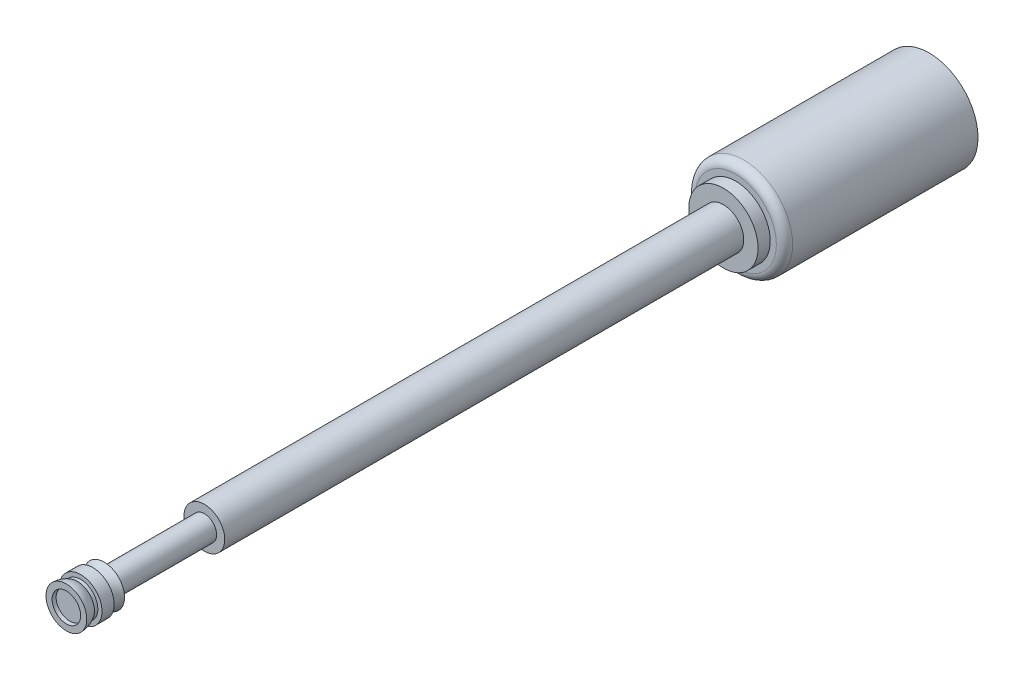
SolidWorks part; units mm, degrees
ref_plane "Front Plane" through (0, 0, 0) normal (0, 0, 1) x (1, 0, 0)
ref_plane "Top Plane" through (0, 0, 0) normal (0, 1, 0) x (1, 0, 0)
ref_plane "Right Plane" through (0, 0, 0) normal (1, 0, 0) x (0, 0, -1)
sketch "Sketch2" plane through (0, 0, 0) normal (0, 0, 1) x (1, 0, 0)
  circle A0 centre (0, 0) radius 0.5
  circle A1 centre (0, 0) radius 1.2
  dimension "D1" = 1
  dimension "D2" = 2.4
extrude "Boss-Extrude1" add sketch "Sketch2" along normal blind 15.5 contours A0 region at (0, 0, 0)
extrude "Boss-Extrude2" add sketch "Sketch2<3>" against normal blind 4.75 contours A1
sketch "Sketch2<3>" plane through (0, 0, 0) normal (0, 0, 1) x (1, 0, 0) same geometry as "Sketch2"
fillet "Fillet1" radius 0.2 1 edges at (1.2, 0, 0)
sketch "Sketch3" plane through (0, 0, 0) normal (0, 0, 1) x (1, 0, 0)
  circle A0 centre (0, 0) radius 0.85
  dimension "D1" = 1.7
extrude "Boss-Extrude3" add sketch "Sketch3" along normal blind 0.3
sketch "Sketch4" plane through (0, 0, 0) normal (0, 1, 0) x (1, 0, 0)
  line L0 (0.5, -15.5) -> (0, -15.5)
  line L1 (-0.5, -15.5) -> (0.5, -15.5) construction
  line L2 (0, -15.5) -> (0, -16.0775)
  line L3 (0.35, -16.4275) -> (0.5, -16.4275)
  line L4 (0.4214, -16.1584) -> (0.4214, -16.0764)
  line L5 (0.4214, -16.0764) -> (0.5238, -16.0764)
  line L6 (0.5238, -16.0764) -> (0.5238, -15.7784)
  line L7 (0.5238, -15.7784) -> (0.4214, -15.7784)
  arc A0 (0, -16.0775) -> (0.35, -16.4275) centre (0, -16.4275) cw
  arc A1 (0.5, -16.4275) -> (0.4214, -16.1584) centre (0, -16.4275) ccw
  arc A2 (0.4214, -15.7784) -> (0.5, -15.5) centre (0.9538, -15.7784) cw
  point P20 (0.425, -16.4275)
  dimension "D2" = 0.35
  dimension "D3" = 0.5
  dimension "D1" = 0.9275
revolve "Revolve1" add sketch "Sketch4" angle 360 about L2
sketch "Sketch5" plane through (0, 0, 0) normal (0, 1, 0) x (1, 0, 0)
  line L0 (0, -15.5) -> (0, -16.4275) construction
  line L1 (0.5, -15.5) -> (-0.5, -15.5) construction
  line L2 (-0.5, -16.4275) -> (0.5, -16.4275) construction
  line L4 (0, -16.3107) -> (-0.4525, -16.3107)
  line L5 (0, -16.3107) -> (0, -16.34)
  line L6 (0, -16.34) -> (-0.4525, -16.34)
  line L7 (-0.4525, -16.3107) -> (-0.4525, -16.34)
  line L8 (0, -16.3107) -> (-0.4525, -16.34) construction
  line L9 (0, -16.34) -> (-0.4525, -16.3107) construction
  point P10 (-0.2262, -16.3254)
  dimension "D1" = 0.84
revolve "Revolve2" add sketch "Sketch5" angle 360 about L0
sketch "Sketch6" plane through (0, 0, 0) normal (0, 1, 0) x (1, 0, 0)
  line L0 (0.5, -15.5) -> (-0.5, -15.5) construction
  line L1 (-0.3, -15.5) -> (-1.3762, -15.5)
  line L2 (-0.3, -15.5) -> (-0.3, -13.04)
  line L3 (-0.3, -13.04) -> (-1.3762, -13.04)
  line L4 (-1.3762, -15.5) -> (-1.3762, -13.04)
  line L5 (-0.3, -15.5) -> (-1.3762, -13.04) construction
  line L6 (-0.3, -13.04) -> (-1.3762, -15.5) construction
  line L7 (0, -15.5) -> (0, -16.7292) construction
  point P4 (-0.8381, -14.27)
  dimension "D1" = 2.46
  dimension "D2" = 0.3
revolve "Cut-Revolve1" cut sketch "Sketch6" angle 360 about L7
sketch "Sketch10" plane through (0, 0, -4.75) normal (0, 0, -1) x (-1, 0, 0)
  point P0 (0, 0)
